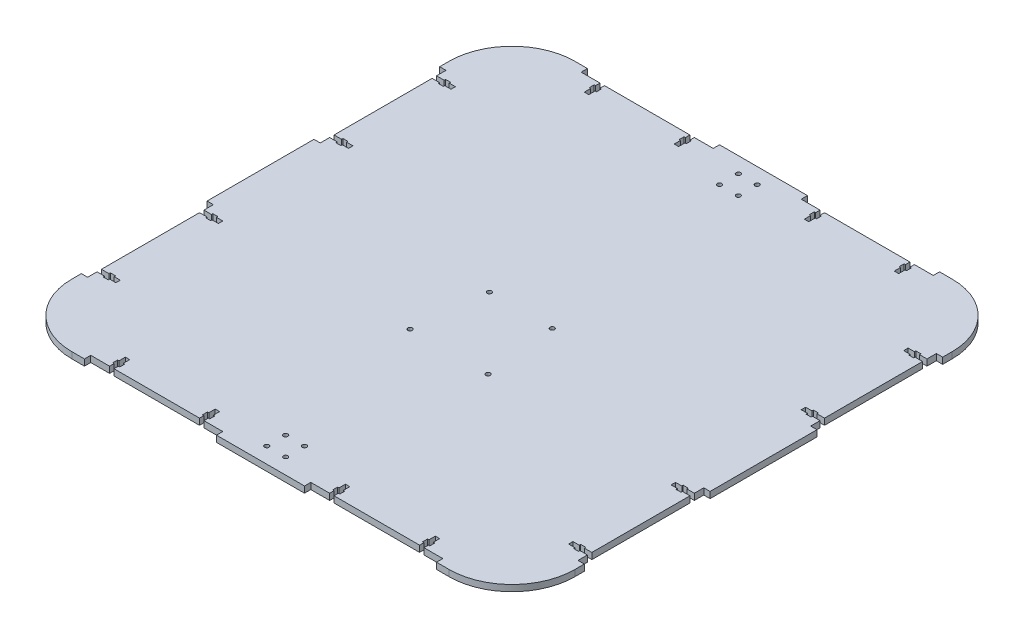
SolidWorks part; units mm, degrees
ref_plane "Front Plane" through (0, 0, 0) normal (0, 0, 1) x (1, 0, 0)
ref_plane "Top Plane" through (0, 0, 0) normal (0, 1, 0) x (1, 0, 0)
ref_plane "Right Plane" through (0, 0, 0) normal (1, 0, 0) x (0, 0, -1)
sketch "Sketch1" plane through (0, 0, 0) normal (0, 1, 0) x (1, 0, 0)
  line L0 (0, -1000) -> (0, 49000) construction
  line L9 (-1000, 0) -> (49000, 0) construction
  line L10 (-10, 190) -> (10, 190)
  line L11 (-10, 190) -> (-10, 170)
  line L12 (-10, 170) -> (10, 170)
  line L13 (10, 190) -> (10, 170)
  line L14 (-1010, 180) -> (48990, 180) construction
  line L15 (-1010, -180) -> (48990, -180) construction
  line L16 (0, 1000) -> (0, -49000) construction
  line L17 (-10, -170) -> (10, -170)
  line L18 (10, -190) -> (10, -170)
  line L19 (-10, -190) -> (10, -190)
  line L20 (-10, -190) -> (-10, -170)
  line L22 (-200, 200) -> (200, 200)
  line L23 (-200, 200) -> (-200, -200)
  line L24 (-200, -200) -> (200, -200)
  line L25 (200, 200) -> (200, -200)
  circle A0 centre (0, 0) radius 200 construction
  circle A1 centre (-7.5, 187.5) radius 1.75
  circle A2 centre (7.5, 187.5) radius 1.75
  circle A3 centre (7.5, 172.5) radius 1.75
  circle A4 centre (-7.5, 172.5) radius 1.75
  circle A5 centre (7.5, -187.5) radius 1.75
  circle A6 centre (-7.5, -187.5) radius 1.75
  circle A7 centre (-7.5, -172.5) radius 1.75
  circle A8 centre (7.5, -172.5) radius 1.75
  point P19 (0, 190)
  point P22 (-10, 180)
  dimension "D1" = 400
  dimension "D7" = 3.5
  dimension "D5" = 20
  dimension "D6" = 180
  dimension "D8" = 2.5
  dimension "D9" = 2.5
extrude "Boss-Extrude2" add sketch "Sketch1" along normal blind 5 contours L25 L22 L23 L24 L10 L13 L12 L11 L19 L20 L17 L18 | L20 L19 L18 L17 A6 A5 A7 A8 | L13 L10 L11 L12 A2 A1 A3 A4 region at (0, 0, -180) region at (0, 0, 180) region at (0, 0, 0)
fillet "Fillet1" radius 50 4 edges at (200, 2.5, -200) (200, 2.5, 200) (-200, 2.5, 200) (-200, 2.5, -200)
sketch "Sketch10" plane through (0, 5, 0) normal (0, 1, 0) x (1, 0, 0)
  line L0 (-150, -200) -> (150, -200) construction
  line L1 (-125, -200) -> (-121.5, -200)
  line L2 (-125, -200) -> (-125, -191.5)
  line L3 (-125, -182.5) -> (-121.5, -182.5)
  line L4 (-121.5, -200) -> (-121.5, -191.5)
  line L6 (-121.5, -187.5) -> (-120.4, -187.5)
  line L7 (-126.1, -187.5) -> (-125, -187.5)
  line L8 (-126.1, -187.5) -> (-126.1, -191.5)
  line L9 (-126.1, -191.5) -> (-125, -191.5)
  line L10 (-120.4, -187.5) -> (-120.4, -191.5)
  line L11 (-121.5, -191.5) -> (-120.4, -191.5)
  line L12 (-125, -187.5) -> (-125, -182.5)
  line L13 (-121.5, -187.5) -> (-121.5, -182.5)
  line L14 (-125, -187.5) -> (-121.5, -187.5) construction
  line L15 (-121.5, -191.5) -> (-125, -191.5) construction
  line L16 (-53.5, -200) -> (-50, -200)
  line L17 (-50, -200) -> (-50, -191.5)
  line L18 (-50, -191.5) -> (-48.9, -191.5)
  line L19 (-48.9, -187.5) -> (-48.9, -191.5)
  line L20 (-50, -187.5) -> (-48.9, -187.5)
  line L21 (-50, -187.5) -> (-50, -182.5)
  line L22 (-53.5, -182.5) -> (-50, -182.5)
  line L23 (-53.5, -187.5) -> (-53.5, -182.5)
  line L24 (-54.6, -187.5) -> (-53.5, -187.5)
  line L25 (-54.6, -187.5) -> (-54.6, -191.5)
  line L26 (-54.6, -191.5) -> (-53.5, -191.5)
  line L27 (-53.5, -200) -> (-53.5, -191.5)
  line L28 (-50, -191.5) -> (-53.5, -191.5) construction
  line L29 (-53.5, -187.5) -> (-50, -187.5) construction
  line L30 (0, -1200) -> (0, 48800) construction
  line L31 (-200, 150) -> (-200, -150) construction
  line L32 (121.5, -191.5) -> (125, -191.5) construction
  line L33 (125, -187.5) -> (121.5, -187.5) construction
  line L34 (125, -200) -> (125, -191.5)
  line L35 (126.1, -191.5) -> (125, -191.5)
  line L36 (126.1, -187.5) -> (126.1, -191.5)
  line L37 (126.1, -187.5) -> (125, -187.5)
  line L38 (125, -187.5) -> (125, -182.5)
  line L39 (125, -182.5) -> (121.5, -182.5)
  line L40 (121.5, -187.5) -> (121.5, -182.5)
  line L41 (121.5, -187.5) -> (120.4, -187.5)
  line L42 (120.4, -187.5) -> (120.4, -191.5)
  line L43 (121.5, -191.5) -> (120.4, -191.5)
  line L44 (121.5, -200) -> (121.5, -191.5)
  line L45 (125, -200) -> (121.5, -200)
  line L46 (53.5, -187.5) -> (50, -187.5) construction
  line L47 (50, -191.5) -> (53.5, -191.5) construction
  line L48 (53.5, -200) -> (53.5, -191.5)
  line L49 (54.6, -191.5) -> (53.5, -191.5)
  line L50 (54.6, -187.5) -> (54.6, -191.5)
  line L51 (54.6, -187.5) -> (53.5, -187.5)
  line L52 (53.5, -187.5) -> (53.5, -182.5)
  line L53 (53.5, -182.5) -> (50, -182.5)
  line L54 (50, -187.5) -> (50, -182.5)
  line L55 (50, -187.5) -> (48.9, -187.5)
  line L56 (48.9, -187.5) -> (48.9, -191.5)
  line L57 (50, -191.5) -> (48.9, -191.5)
  line L58 (50, -200) -> (50, -191.5)
  line L59 (53.5, -200) -> (50, -200)
  line L60 (-1000, 0) -> (49000, 0) construction
  line L61 (125, 200) -> (121.5, 200)
  line L62 (121.5, 200) -> (121.5, 191.5)
  line L63 (121.5, 191.5) -> (120.4, 191.5)
  line L64 (120.4, 187.5) -> (120.4, 191.5)
  line L65 (121.5, 187.5) -> (120.4, 187.5)
  line L66 (121.5, 187.5) -> (121.5, 182.5)
  line L67 (125, 182.5) -> (121.5, 182.5)
  line L68 (125, 187.5) -> (125, 182.5)
  line L69 (126.1, 187.5) -> (125, 187.5)
  line L70 (126.1, 187.5) -> (126.1, 191.5)
  line L71 (126.1, 191.5) -> (125, 191.5)
  line L72 (125, 200) -> (125, 191.5)
  line L73 (53.5, 200) -> (50, 200)
  line L74 (50, 200) -> (50, 191.5)
  line L75 (50, 191.5) -> (48.9, 191.5)
  line L76 (48.9, 187.5) -> (48.9, 191.5)
  line L77 (50, 187.5) -> (48.9, 187.5)
  line L78 (50, 187.5) -> (50, 182.5)
  line L79 (53.5, 182.5) -> (50, 182.5)
  line L80 (53.5, 187.5) -> (53.5, 182.5)
  line L81 (54.6, 187.5) -> (53.5, 187.5)
  line L82 (54.6, 187.5) -> (54.6, 191.5)
  line L83 (54.6, 191.5) -> (53.5, 191.5)
  line L84 (53.5, 200) -> (53.5, 191.5)
  line L85 (-53.5, 200) -> (-53.5, 191.5)
  line L86 (-54.6, 191.5) -> (-53.5, 191.5)
  line L87 (-54.6, 187.5) -> (-54.6, 191.5)
  line L88 (-54.6, 187.5) -> (-53.5, 187.5)
  line L89 (-53.5, 187.5) -> (-53.5, 182.5)
  line L90 (-53.5, 182.5) -> (-50, 182.5)
  line L91 (-50, 187.5) -> (-50, 182.5)
  line L92 (-50, 187.5) -> (-48.9, 187.5)
  line L93 (-48.9, 187.5) -> (-48.9, 191.5)
  line L94 (-50, 191.5) -> (-48.9, 191.5)
  line L95 (-50, 200) -> (-50, 191.5)
  line L96 (-53.5, 200) -> (-50, 200)
  line L97 (-125, 200) -> (-125, 191.5)
  line L98 (-126.1, 191.5) -> (-125, 191.5)
  line L99 (-126.1, 187.5) -> (-126.1, 191.5)
  line L100 (-126.1, 187.5) -> (-125, 187.5)
  line L101 (-125, 187.5) -> (-125, 182.5)
  line L102 (-125, 182.5) -> (-121.5, 182.5)
  line L103 (-121.5, 187.5) -> (-121.5, 182.5)
  line L104 (-121.5, 187.5) -> (-120.4, 187.5)
  line L105 (-120.4, 187.5) -> (-120.4, 191.5)
  line L106 (-121.5, 191.5) -> (-120.4, 191.5)
  line L107 (-121.5, 200) -> (-121.5, 191.5)
  line L108 (-125, 200) -> (-121.5, 200)
  point P11 (-123.25, -200)
  point P15 (-123.25, -191.5)
  point P16 (-123.25, -187.5)
  point P17 (-123.25, -182.5)
  point P33 (0, -200)
  dimension "D1" = 3.5
  dimension "D2" = 5.7
  dimension "D3" = 5
  dimension "D4" = 4
  dimension "D5" = 1.1
  dimension "D7" = 75
  dimension "D8" = 50
  dimension "D9" = 17.5
  dimension "D6" = 2
extrude "Cut-Extrude8" cut sketch "Sketch10" against normal blind 10
sketch "Sketch11" plane through (0, 5, 0) normal (0, 1, 0) x (1, 0, 0)
  line L0 (-150, -200) -> (-125, -200) construction
  line L1 (-140, -200) -> (-35, -200)
  line L2 (-140, -200) -> (-140, -195)
  line L3 (-140, -195) -> (-35, -195)
  line L4 (-35, -200) -> (-35, -195)
  line L5 (-50, -200) -> (-50, -191.5) construction
  line L6 (-125, -191.5) -> (-125, -200) construction
  line L7 (0, -1200) -> (0, 48800) construction
  line L8 (-50, -200) -> (50, -200) construction
  line L9 (-1200, 0) -> (48800, 0) construction
  line L10 (-200, 150) -> (-200, -150) construction
  line L11 (140, -195) -> (35, -195)
  line L12 (35, -200) -> (35, -195)
  line L13 (140, -200) -> (35, -200)
  line L14 (140, -200) -> (140, -195)
  line L15 (140, 200) -> (140, 195)
  line L16 (140, 200) -> (35, 200)
  line L17 (35, 200) -> (35, 195)
  line L18 (140, 195) -> (35, 195)
  line L19 (-140, 195) -> (-35, 195)
  line L20 (-35, 200) -> (-35, 195)
  line L21 (-140, 200) -> (-35, 200)
  line L22 (-140, 200) -> (-140, 195)
  point P15 (0, -200)
  point P20 (-200, 0)
  dimension "D1" = 5
  dimension "D2" = 15
  dimension "D3" = 15
extrude "Cut-Extrude9" cut sketch "Sketch11" against normal blind 10
sketch "Sketch12" plane through (0, 5, 0) normal (0, 1, 0) x (1, 0, 0)
  line L0 (-200, 150) -> (-200, -150) construction
  line L1 (-200, 135) -> (-189, 135)
  line L2 (-200, 135) -> (-200, 131.5)
  line L3 (-200, 131.5) -> (-189, 131.5)
  line L4 (-180, 135) -> (-180, 131.5)
  line L5 (-200, 53.5) -> (-189, 53.5)
  line L6 (-189, 131.5) -> (-189, 130.4)
  line L7 (-189, 136.1) -> (-185, 136.1)
  line L8 (-189, 136.1) -> (-189, 135)
  line L9 (-189, 130.4) -> (-185, 130.4)
  line L10 (-185, 136.1) -> (-185, 135)
  line L11 (-185, 131.5) -> (-185, 130.4)
  line L12 (-185, 135) -> (-180, 135)
  line L13 (-185, 131.5) -> (-180, 131.5)
  line L14 (-189, 135) -> (-189, 131.5) construction
  line L15 (-185, 131.5) -> (-185, 135) construction
  line L16 (-189, 54.6) -> (-189, 53.5)
  line L17 (-189, 54.6) -> (-185, 54.6)
  line L18 (-185, 54.6) -> (-185, 53.5)
  line L19 (-185, 53.5) -> (-180, 53.5)
  line L20 (-180, 53.5) -> (-180, 50)
  line L21 (-185, 50) -> (-180, 50)
  line L22 (-185, 50) -> (-185, 48.9)
  line L23 (-189, 48.9) -> (-185, 48.9)
  line L24 (-189, 50) -> (-189, 48.9)
  line L25 (-200, 50) -> (-189, 50)
  line L26 (-200, 53.5) -> (-200, 50)
  line L27 (-1200, 0) -> (48800, 0) construction
  line L28 (-200, -53.5) -> (-200, -50)
  line L29 (-200, -50) -> (-189, -50)
  line L30 (-189, -50) -> (-189, -48.9)
  line L31 (-189, -48.9) -> (-185, -48.9)
  line L32 (-185, -50) -> (-185, -48.9)
  line L33 (-185, -50) -> (-180, -50)
  line L34 (-180, -53.5) -> (-180, -50)
  line L35 (-185, -53.5) -> (-180, -53.5)
  line L36 (-185, -54.6) -> (-185, -53.5)
  line L37 (-189, -54.6) -> (-185, -54.6)
  line L38 (-189, -54.6) -> (-189, -53.5)
  line L39 (-200, -53.5) -> (-189, -53.5)
  line L40 (-200, -135) -> (-200, -131.5)
  line L41 (-200, -131.5) -> (-189, -131.5)
  line L42 (-189, -131.5) -> (-189, -130.4)
  line L43 (-189, -130.4) -> (-185, -130.4)
  line L44 (-185, -131.5) -> (-185, -130.4)
  line L45 (-185, -131.5) -> (-180, -131.5)
  line L46 (-180, -135) -> (-180, -131.5)
  line L47 (-185, -135) -> (-180, -135)
  line L48 (-185, -136.1) -> (-185, -135)
  line L49 (-189, -136.1) -> (-185, -136.1)
  line L50 (-189, -136.1) -> (-189, -135)
  line L51 (-200, -135) -> (-189, -135)
  line L52 (0, -1200) -> (0, 48800) construction
  line L53 (-35, -200) -> (35, -200) construction
  line L54 (200, -135) -> (189, -135)
  line L55 (189, -136.1) -> (189, -135)
  line L56 (189, -136.1) -> (185, -136.1)
  line L57 (185, -136.1) -> (185, -135)
  line L58 (185, -135) -> (180, -135)
  line L59 (180, -135) -> (180, -131.5)
  line L60 (185, -131.5) -> (180, -131.5)
  line L61 (185, -131.5) -> (185, -130.4)
  line L62 (189, -130.4) -> (185, -130.4)
  line L63 (189, -131.5) -> (189, -130.4)
  line L64 (200, -131.5) -> (189, -131.5)
  line L65 (200, -135) -> (200, -131.5)
  line L66 (200, -53.5) -> (189, -53.5)
  line L67 (189, -54.6) -> (189, -53.5)
  line L68 (189, -54.6) -> (185, -54.6)
  line L69 (185, -54.6) -> (185, -53.5)
  line L70 (185, -53.5) -> (180, -53.5)
  line L71 (180, -53.5) -> (180, -50)
  line L72 (185, -50) -> (180, -50)
  line L73 (185, -50) -> (185, -48.9)
  line L74 (189, -48.9) -> (185, -48.9)
  line L75 (189, -50) -> (189, -48.9)
  line L76 (200, -50) -> (189, -50)
  line L77 (200, -53.5) -> (200, -50)
  line L78 (200, 53.5) -> (200, 50)
  line L79 (200, 50) -> (189, 50)
  line L80 (189, 50) -> (189, 48.9)
  line L81 (189, 48.9) -> (185, 48.9)
  line L82 (185, 50) -> (185, 48.9)
  line L83 (185, 50) -> (180, 50)
  line L84 (180, 53.5) -> (180, 50)
  line L85 (185, 53.5) -> (180, 53.5)
  line L86 (185, 54.6) -> (185, 53.5)
  line L87 (189, 54.6) -> (185, 54.6)
  line L88 (189, 54.6) -> (189, 53.5)
  line L89 (200, 53.5) -> (189, 53.5)
  line L90 (200, 135) -> (200, 131.5)
  line L91 (200, 131.5) -> (189, 131.5)
  line L92 (189, 131.5) -> (189, 130.4)
  line L93 (189, 130.4) -> (185, 130.4)
  line L94 (185, 131.5) -> (185, 130.4)
  line L95 (185, 131.5) -> (180, 131.5)
  line L96 (180, 135) -> (180, 131.5)
  line L97 (185, 135) -> (180, 135)
  line L98 (185, 136.1) -> (185, 135)
  line L99 (189, 136.1) -> (185, 136.1)
  line L100 (189, 136.1) -> (189, 135)
  line L101 (200, 135) -> (189, 135)
  point P31 (-200, 0)
  point P60 (0, -200)
  dimension "D1" = 20
  dimension "D2" = 3.5
  dimension "D3" = 5.7
  dimension "D4" = 5
  dimension "D5" = 4
  dimension "D6" = 15
  dimension "D7" = 1.1
  dimension "D9" = 50
  dimension "D8" = 2
extrude "Cut-Extrude10" cut sketch "Sketch12" against normal blind 5
sketch "Sketch13" plane through (0, 5, 0) normal (0, 1, 0) x (1, 0, 0)
  line L0 (-200, 150) -> (-200, 135) construction
  line L1 (-200, 142.5) -> (-195, 142.5)
  line L2 (-200, 142.5) -> (-200, 42.5)
  line L3 (-200, 42.5) -> (-195, 42.5)
  line L4 (-195, 142.5) -> (-195, 42.5)
  line L6 (-200, 50) -> (-189, 50) construction
  line L7 (-1200, 0) -> (48800, 0) construction
  line L8 (-200, 50) -> (-200, -50) construction
  line L9 (0, -800) -> (0, 49200) construction
  line L10 (-35, 200) -> (35, 200) construction
  line L11 (-200, -42.5) -> (-195, -42.5)
  line L12 (-195, -142.5) -> (-195, -42.5)
  line L13 (-200, -142.5) -> (-195, -142.5)
  line L14 (-200, -142.5) -> (-200, -42.5)
  line L15 (0, 800) -> (0, -49200) construction
  line L16 (200, -142.5) -> (200, -42.5)
  line L17 (200, -142.5) -> (195, -142.5)
  line L18 (195, -142.5) -> (195, -42.5)
  line L19 (200, -42.5) -> (195, -42.5)
  line L20 (200, 42.5) -> (195, 42.5)
  line L21 (195, 142.5) -> (195, 42.5)
  line L22 (200, 142.5) -> (195, 142.5)
  line L23 (200, 142.5) -> (200, 42.5)
  point P13 (-200, 0)
  point P18 (0, 200)
  dimension "D1" = 7.5
  dimension "D2" = 5
extrude "Cut-Extrude11" cut sketch "Sketch13" against normal blind 5
sketch "Sketch14" plane through (0, 5, 0) normal (0, 1, 0) x (1, 0, 0)
  line L0 (-31, -50) -> (31, -50) construction
  line L1 (-25, 7) -> (25, 7) construction
  circle A0 centre (-31, -50) radius 1.75
  circle A1 centre (31, -50) radius 1.75
  circle A2 centre (-25, 7) radius 1.75
  circle A3 centre (25, 7) radius 1.75
  point P4 (0, -50)
  point P7 (0, 7)
  dimension "D1" = 3.5
  dimension "D2" = 62
  dimension "D3" = 50
  dimension "D4" = 50
  dimension "D5" = 57
extrude "Cut-Extrude12" cut sketch "Sketch14" against normal blind 10
